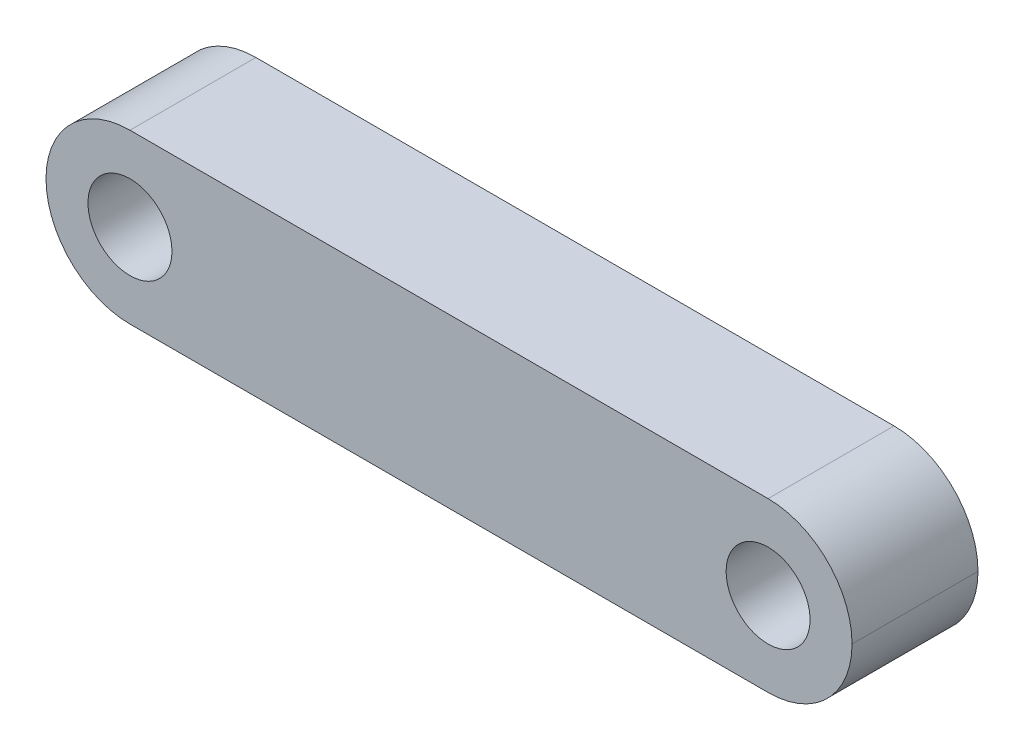
SolidWorks part; units mm, degrees
ref_plane "Ön Düzlem" through (0, 0, 0) normal (0, 0, 1) x (1, 0, 0)
ref_plane "Üst Düzlem" through (0, 0, 0) normal (0, 1, 0) x (1, 0, 0)
ref_plane "Sağ Düzlem" through (0, 0, 0) normal (1, 0, 0) x (0, 0, -1)
sketch "Çizim1" plane through (0, 0, 0) normal (0, 0, 1) x (1, 0, 0)
  line L0 (0, 20) -> (0, -20) construction
  line L1 (-96, 20) -> (96, 20)
  line L2 (-96, 20) -> (-96, -20)
  line L3 (-96, -20) -> (96, -20)
  line L4 (96, 20) -> (96, -20)
  line L5 (-96, 20) -> (96, -20) construction
  line L6 (-96, -20) -> (96, 20) construction
  circle A0 centre (-76, 0) radius 10
  circle A1 centre (76, 0) radius 10
  point P0 (0, 0)
  dimension "D3" = 20
  dimension "D4" = 20
  dimension "D5" = 20
  dimension "D1" = 40
  dimension "D2" = 192
extrude "Yükseklik-Ekstrüzyon1" add sketch "Çizim1" along normal mid plane 30
fillet "Radyus1" radius 20 4 edges at (-96, -20, 0) (-96, 20, 0) (96, -20, 0) (96, 20, 0)
ref_plane "Plane1" through (0, 0, 0) normal (0, 0, 1) x (1, 0, 0)
sketch "Sketch2" plane through (0, 0, 0) normal (0, 0, 1) x (1, 0, 0)
  point P0 (-76, 0)
  point P1 (76, 0)
